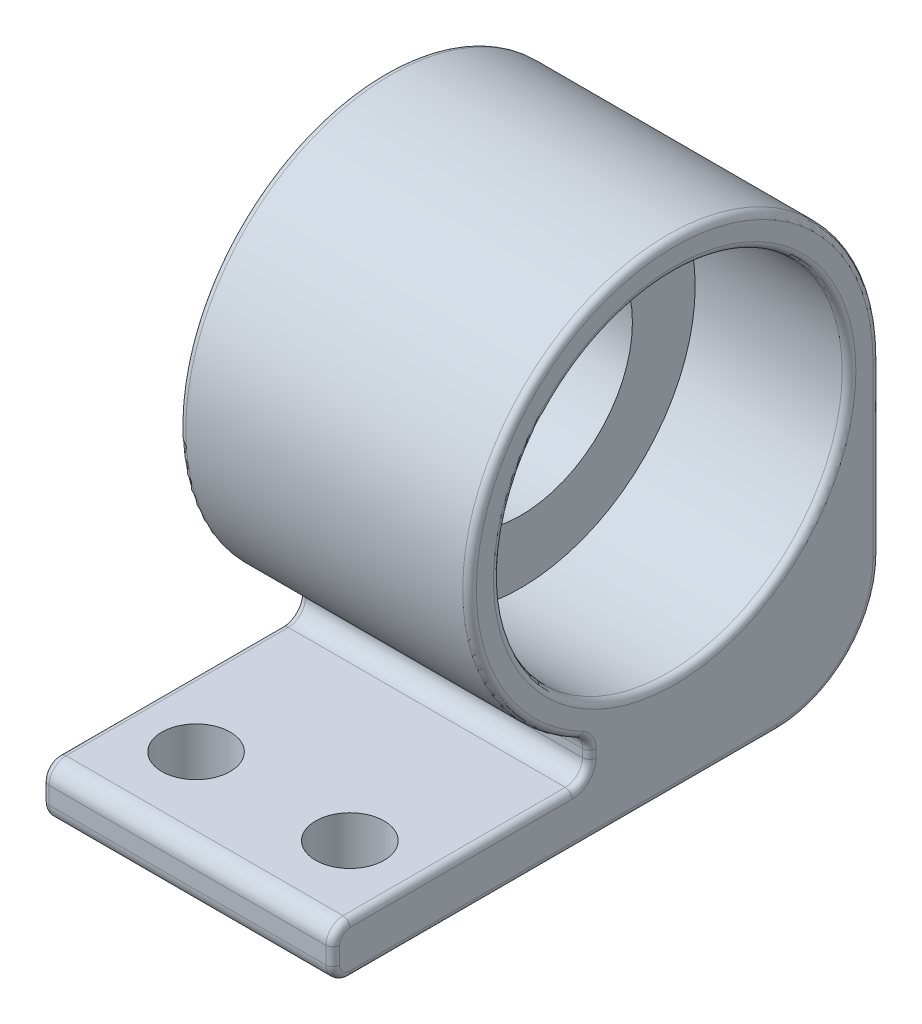
SolidWorks part; units mm, degrees
ref_plane "前视基准面" through (0, 0, 0) normal (0, 0, 1) x (1, 0, 0)
ref_plane "上视基准面" through (0, 0, 0) normal (0, 1, 0) x (1, 0, 0)
ref_plane "右视基准面" through (0, 0, 0) normal (1, 0, 0) x (0, 0, -1)
sketch "草图1" plane through (0, 0, 0) normal (1, 0, 0) x (0, 0, -1)
  line L0 (-9.5, -6.5) -> (-3, -6.5)
  line L1 (-10, -7) -> (-10, -7.5)
  line L3 (6, 0) -> (6, -5)
  line L5 (-9.5, -8) -> (3, -8)
  line L7 (-2.5, -5.7663) -> (-2.5, -6)
  arc A0 (6, 0) -> (-2.7692, -5.3227) centre (0, 0) ccw
  arc A1 (6, -5) -> (3, -8) centre (3, -5) cw
  arc A3 (-9.5, -6.5) -> (-10, -7) centre (-9.5, -7) ccw
  arc A4 (-9.5, -8) -> (-10, -7.5) centre (-9.5, -7.5) cw
  arc A7 (-2.5, -6) -> (-3, -6.5) centre (-3, -6) cw
  arc A8 (-2.5, -5.7663) -> (-2.7692, -5.3227) centre (-3, -5.7663) ccw
  point P14 (3.9686, -6.5)
  dimension "D1" = 6.5
  dimension "D2" = 3
  dimension "D9" = 8
extrude "凸台-拉伸1" add sketch "草图1" along normal blind 8.5
sketch "草图2" plane through (0, 0, 0) normal (-1, 0, 0) x (0, 0, 1)
  circle A0 centre (0, 0) radius 2
extrude "切除-拉伸1" cut sketch "草图2" against normal blind 10
sketch "草图6" plane through (8.5, 0, 0) normal (1, 0, 0) x (0, 0, -1)
  circle A0 centre (0, 0) radius 5.1
extrude "切除-拉伸3" cut sketch "草图6" against normal blind 4.5
hole_wizard "5/16-18 螺纹孔1" positions "草图3" profile "草图4" tap size "5/16-18" standard "ANSI Inch"
sketch "草图3" plane through (4, 0, 0) normal (1, 0, 0) x (0, 0, -1)
  point P0 (0, 0)
sketch "草图4" plane through (4, 0, 0) normal (0, 1, 0) x (0, 0, -1)
  line L0 (0, 0) -> (0, 5.1611)
  line L1 (0, 5.1611) -> (3.2639, 3.2)
  line L2 (3.2639, 3.2) -> (3.2639, 0)
  line L5 (3.2639, 0) -> (0, 0)
  line L10 (0, 5.1611) -> (-3.2639, 3.2) construction
  line L11 (0, -6.35) -> (0, 107.95) construction
  dimension "螺纹孔钻头直径" = 6.5278
  dimension "螺纹孔钻头深度" = 3.2
  dimension "导头角度" = 118
cosmetic thread "孔螺蚊线1" parameters "D1"=3.2, "D2"=7.9375
sketch "草图5" plane through (0, -6.5, 0) normal (0, 1, 0) x (1, 0, 0)
  line L0 (0, -9.5) -> (0, 3) construction
  line L1 (8.5, -3) -> (8.5, -9.5) construction
  circle A0 centre (2, -7.5) radius 1
  circle A1 centre (6.5, -7.5) radius 1
  dimension "D1" = 2
  dimension "D2" = 2
extrude "切除-拉伸2" cut sketch "草图5" against normal up to next
fillet "圆角1" radius 0.2 24 edges at (0, -5.8831, 2.5) (0, -6.3536, 2.6464) (0, -6.5, 6.25) (0, -6.6464, 9.8536) (0, -7.25, 10) (0, -7.8536, 9.8536) (0, -8, 3.25) (0, 5.1291, 3.1132) (0, -5.5068, 2.5726) (0, 0, 2) (8.5, 5.1291, 3.1132) (8.5, -8, 3.25) (8.5, -7.8536, 9.8536) (8.5, -7.25, 10) (8.5, -6.6464, 9.8536) (8.5, -6.5, 6.25) (8.5, -6.3536, 2.6464) (8.5, -5.8831, 2.5) (8.5, -5.5068, 2.5726) (8.5, 0, -5.1) (0, -7.1213, -5.1213) (0, -2.5, -6) (8.5, -2.5, -6) (8.5, -7.1213, -5.1213)
